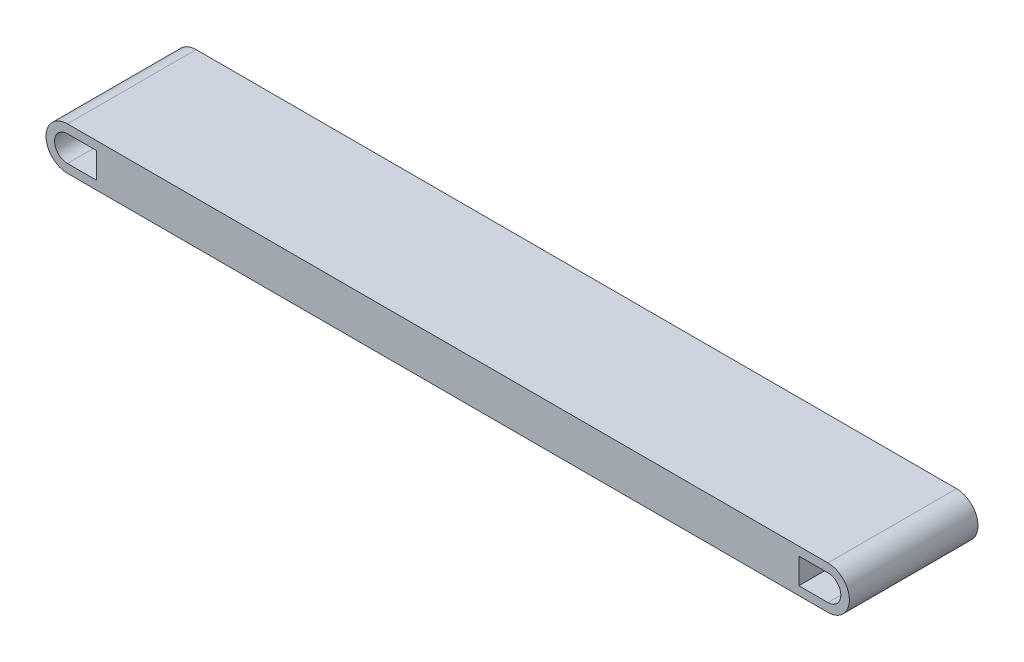
SolidWorks part; units mm, degrees
material "1060 Alloy"
ref_plane "Front Plane" through (0, 0, 0) normal (0, 0, 1) x (1, 0, 0)
ref_plane "Top Plane" through (0, 0, 0) normal (0, 1, 0) x (1, 0, 0)
ref_plane "Right Plane" through (0, 0, 0) normal (1, 0, 0) x (0, 0, -1)
sketch "Sketch1" plane through (0, 0, 0) normal (0, 1, 0) x (1, 0, 0)
  line L1 (-50.8, 9.525) -> (50.8, 9.525)
  line L2 (-50.8, 9.525) -> (-50.8, -9.525)
  line L3 (-50.8, -9.525) -> (50.8, -9.525)
  line L4 (50.8, 9.525) -> (50.8, -9.525)
  line L5 (-50.8, 9.525) -> (50.8, -9.525) construction
  line L6 (-50.8, -9.525) -> (50.8, 9.525) construction
  point P0 (0, 0)
  dimension "D1" = 19.05
  dimension "D2" = 101.6
extrude "Boss-Extrude1" add sketch "Sketch1" along normal blind 6.35
sketch "Sketch2" plane through (0, 0, 9.525) normal (0, 0, 1) x (1, 0, 0)
  line L0 (-42.5768, 6.35) -> (-50.8, 6.35)
  line L1 (-50.8, 6.35) -> (50.8, 6.35) construction
  line L2 (-50.8, 6.35) -> (-50.8, 0) construction
  line L3 (-50.8, 6.35) -> (-56.3139, 6.35)
  line L4 (-56.3139, 0) -> (-50.8, 0)
  line L5 (-50.8, 6.35) -> (-50.8, 0)
  line L6 (-56.3139, 5.08) -> (-52.0058, 5.08)
  line L7 (-52.0058, 5.08) -> (-52.0058, 1.27)
  line L8 (-52.0058, 1.27) -> (-56.3139, 1.27)
  arc A0 (-56.3139, 0) -> (-56.3139, 6.35) centre (-56.3139, 3.175) cw
  arc A1 (-56.3139, 5.08) -> (-56.3139, 1.27) centre (-56.3139, 3.175) ccw
  line M4 (-50.8, 6.35) -> (-50.8, 0)
  dimension "D1" = 1.27
  dimension "D2" = 3.81
extrude "Boss-Extrude2" add sketch "Sketch2" against normal up to surface (19.05 mm away) contours A0 L4 L3 M4 region at (-50.9076, 3.175, 9.525) up to face at (0, 3.175, -9.525)
mirror "Mirror1" about plane through (0, 0, 0) normal (1, 0, 0) of "Boss-Extrude2"
